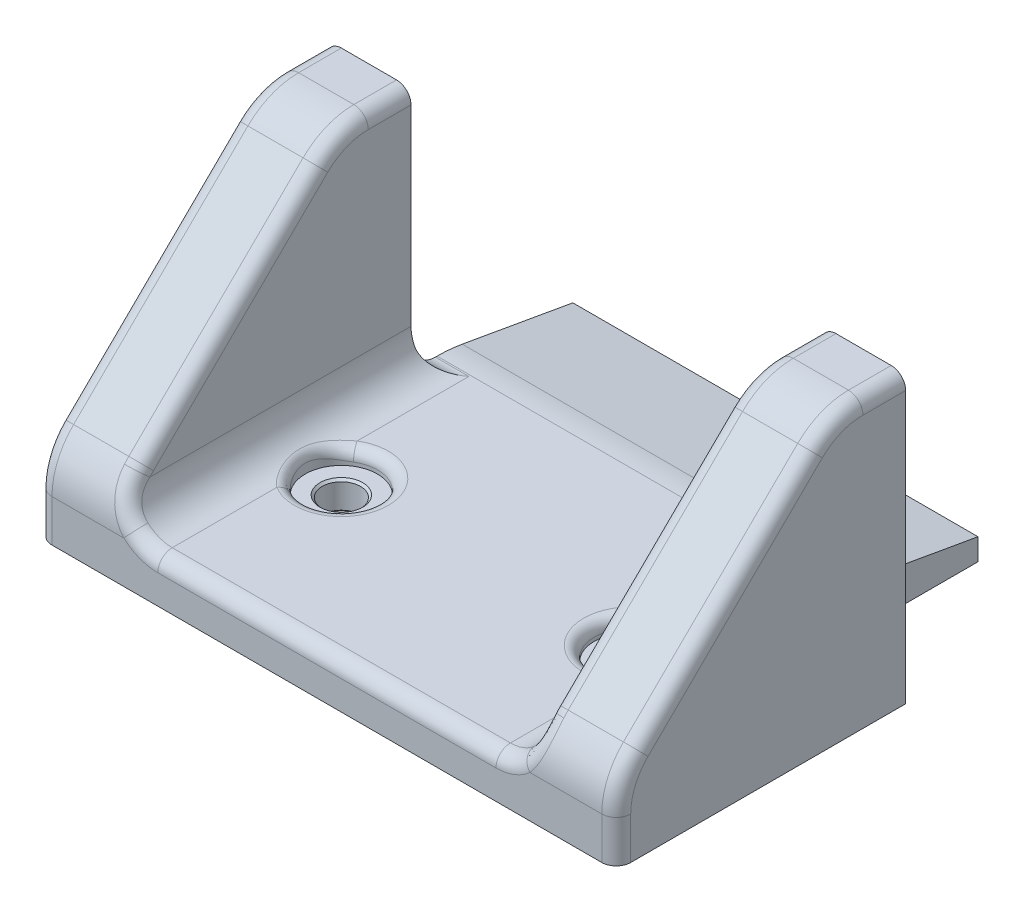
SolidWorks part; units mm, degrees
ref_plane "Front Plane" through (0, 0, 0) normal (0, 0, 1) x (1, 0, 0)
ref_plane "Top Plane" through (0, 0, 0) normal (0, 1, 0) x (1, 0, 0)
ref_plane "Right Plane" through (0, 0, 0) normal (1, 0, 0) x (0, 0, -1)
sketch "Sketch1" plane through (0, 0, 0) normal (0, 0, 1) x (1, 0, 0)
  line L9 (-40, -160) -> (-40, 0) construction
  line L10 (-40, -160) -> (40, -160) construction
  line L11 (-40, 0) -> (40, 0) construction
  line L12 (40, -160) -> (40, 0) construction
  line L13 (-40, -160) -> (40, 0) construction
  line L14 (-40, 0) -> (40, -160) construction
  point P0 (56.1234, 47.8891)
  point P1 (0, 0)
  point P17 (0, -80)
  line B0 (-28.37, 0) -> (28.37, 0) construction
  line B1 (-39.45, 39.5) -> (-39.45, 0) construction
  line B2 (-39.45, 0) -> (-28.37, 0) construction
  line B3 (-28.37, 0) -> (-28.37, 39.5) construction
  line B4 (-28.37, 39.5) -> (-39.45, 39.5) construction
  line B5 (39.45, 0) -> (39.45, 39.5) construction
  line B6 (39.45, 39.5) -> (28.37, 39.5) construction
  line B7 (28.37, 39.5) -> (28.37, 0) construction
  line B8 (28.37, 0) -> (39.45, 0) construction
  circle B9 centre (-34.45, 27.75) radius 2.95 construction
  circle B10 centre (-34.45, 11.75) radius 2.95 construction
  circle B11 centre (34.45, 27.75) radius 2.95 construction
  circle B12 centre (34.45, 11.75) radius 2.95 construction
  dimension "D1" = 80
  dimension "D2" = 160
sketch_block_instance "Block1-1"
sketch_block "Block1"
sketch "Sketch3" plane through (0, 0, 0) normal (1, 0, 0) x (0, 0, -1)
  line L0 (0, 0) -> (0, 39.5)
  line L1 (0, 39.5) -> (-10, 39.5)
  line L2 (-10, 39.5) -> (-40, 10)
  line L3 (-40, 10) -> (-40, 0)
  line L4 (-40, 0) -> (0, 0)
  point P3 (-41.289, 10)
  dimension "D1" = 10
  dimension "D2" = 10
  dimension "D3" = 40
extrude "Boss-Extrude1" add sketch "Sketch3" along normal mid plane 80
sketch "Sketch4" plane through (0, 0, 0) normal (0, 0, 1) x (1, 0, 0)
  line L0 (28.37, 39.5) -> (28.37, 6)
  line L1 (28.37, 39.5) -> (28.37, 0) construction
  line L2 (28.37, 6) -> (-28.37, 6)
  line L3 (-28.37, 0) -> (-28.37, 39.5) construction
  line L4 (-28.37, 6) -> (-28.37, 39.5)
  line L5 (-40, 0) -> (40, 0) construction
  line L6 (28.37, 39.5) -> (-28.37, 39.5)
  dimension "D1" = 6
extrude "Cut-Extrude1" cut sketch "Sketch4" along normal through all
sketch "Sketch5" plane through (0, 0, 0) normal (0, 0, -1) x (-1, 0, 0)
  circle A0 centre (-34.45, 27.75) radius 2.375
  circle A1 centre (34.45, 27.75) radius 2.375
  circle A2 centre (34.45, 11.75) radius 2.375
  circle A3 centre (-34.45, 11.75) radius 2.375
  dimension "D1" = 4.75
extrude "Cut-Extrude2" cut sketch "Sketch5" against normal blind 14
chamfer "Chamfer1" distance 2 angle 45 4 edges at (-36.825, 11.75, 14) (-36.825, 27.75, 14) (32.075, 11.75, 14) (32.075, 27.75, 14)
sketch "Sketch6" plane through (0, 6, 0) normal (0, 1, 0) x (1, 0, 0)
  line L0 (-28, 0) -> (-28, 22)
  line L1 (-40, 0) -> (40, 0) construction
  line L2 (-28, 22) -> (28, 22)
  line L3 (28, 22) -> (28, 0)
  line L4 (-40, 0) -> (40, 0) construction
  line L5 (0, 0) -> (0, 22) construction
  line L6 (28, 0) -> (-28, 0)
  dimension "D1" = 22
  dimension "D2" = 56
extrude "Boss-Extrude2" add sketch "Sketch6" against normal up to surface (6 mm away) up to face at (0, 0, 20)
fillet "Fillet2" radius 5 2 edges at (-28.37, 6, 20) (28.37, 6, 20)
sketch "Sketch7" plane through (0, 6, 0) normal (0, 1, 0) x (1, 0, 0)
  line L1 (-28, 22) -> (28, 22)
  line L2 (-28, 22) -> (-28, 0)
  line L3 (-28, 0) -> (28, 0)
  line L4 (28, 22) -> (28, 0)
  line L5 (0, 0) -> (0, 22) construction
  line L6 (-28, 11) -> (28, 11) construction
  point P172 (0, 11)
extrude "Cut-Extrude3" cut sketch "Sketch7" along normal through all
fillet "Fillet3" radius 3 2 edges at (-25.685, 6, 0) (25.685, 6, 0)
chamfer "Chamfer2" distance 3 angle 80 1 edges at (0, 6, -22) first distance on face at (0, 3, -22)
fillet "Fillet4" radius 20 1 edges at (0, 6, -4.9862)
fillet "Fillet5" radius 10 3 edges at (-34.1345, 10, 40) (34.185, 39.5, 10) (-34.185, 39.5, 10)
fillet "Fillet6" radius 2 21 edges at (40, 39.5, 2.9535) (40, 2.9043, 40) (40, 9.6742, 39.2226) (40, 24.7845, 24.9649) (-40, 2.9043, 40) (-40, 9.6742, 39.2226) (-40, 24.7845, 24.9649) (-40, 38.7548, 9.695) (-28.37, 39.5, 2.9535) (-28.37, 38.7548, 9.695) (-28.37, 24.7845, 24.9649) (-28.37, 12.017, 37.8393) (-27.4116, 8.0563, 39.7441) (0, 6, 39.9982) (26.4838, 7.0879, 39.9178) (28.37, 12.017, 37.8393) (28.37, 24.7845, 24.9649) (28.37, 39.5, 2.9535) (40, 38.7548, 9.695) (-40, 39.5, 2.9535) (28.37, 38.7548, 9.695)
sketch "Sketch8" plane through (0, 6, 0) normal (0, 1, 0) x (1, 0, 0)
  line L0 (0, 0) -> (0, -40) construction
  line L1 (23.37, -40) -> (-23.37, -40) construction
  line L2 (-20, -18) -> (20, -18) construction
  circle A0 centre (-20, -18) radius 2.65
  circle A1 centre (20, -18) radius 2.65
  point P8 (0, -18)
  dimension "D1" = 5.3
  dimension "D2" = 40
  dimension "D3" = 22
extrude "Cut-Extrude4" cut sketch "Sketch8" against normal through all
sketch "Sketch9" plane through (0, 6, 0) normal (0, 1, 0) x (1, 0, 0)
  circle A0 centre (-20, -18) radius 5
  circle A1 centre (20, -18) radius 5
  dimension "D1" = 10
extrude "Cut-Extrude5" cut sketch "Sketch9" against normal blind 2 and the other way through all
fillet "Fillet7" radius 1.5 4 edges at (15, 6, 18) (-24.9281, 6.249, 17.1552) (24.9281, 6.249, 18.8448) (-15, 6, 18)
chamfer "Chamfer3" distance 0.3 angle 45 4 edges at (17.35, 0, 18) (-22.65, 0, 18) (17.35, 4, 18) (-22.65, 4, 18)
